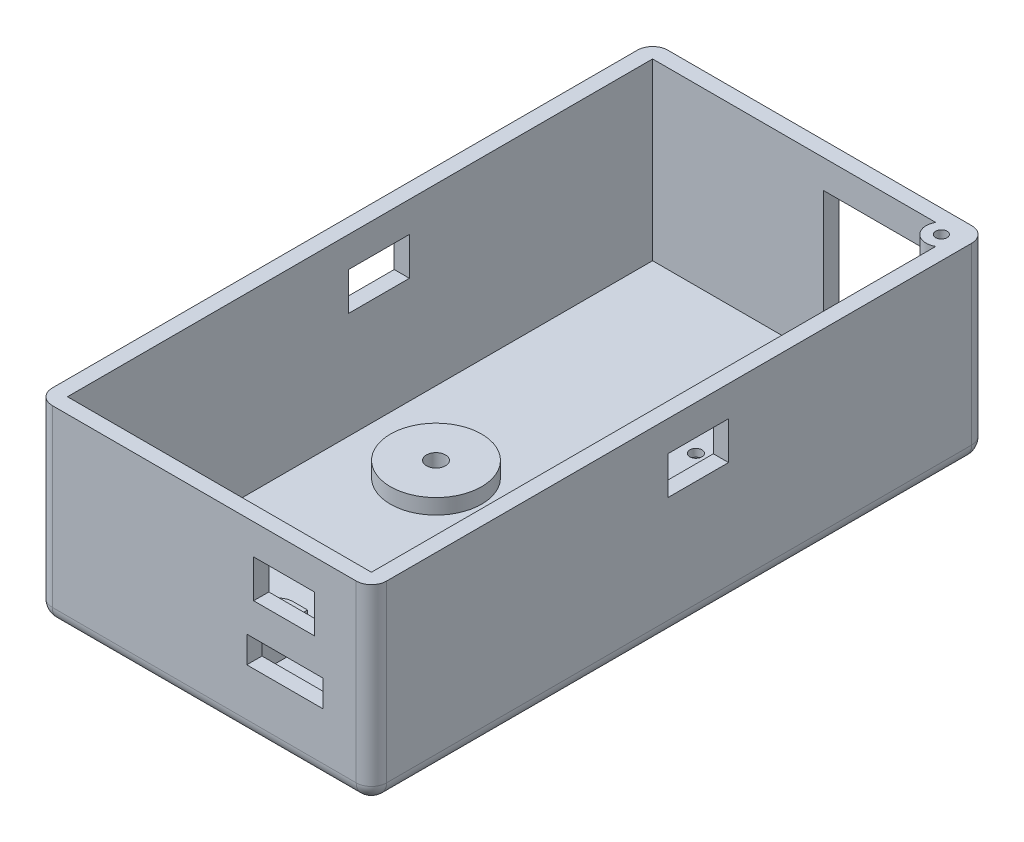
SolidWorks part; units mm, degrees
ref_plane "前视基准面" through (0, 0, 0) normal (0, 0, 1) x (1, 0, 0)
ref_plane "上视基准面" through (0, 0, 0) normal (0, 1, 0) x (1, 0, 0)
ref_plane "右视基准面" through (0, 0, 0) normal (1, 0, 0) x (0, 0, -1)
sketch "草图1" plane through (0, 0, 0) normal (0, 1, 0) x (1, 0, 0)
  line L1 (-22, 38) -> (22, 38)
  line L2 (-22, 38) -> (-22, -43)
  line L3 (-22, -43) -> (22, -43)
  line L4 (22, 38) -> (22, -43)
  dimension "D1" = 81
  dimension "D2" = 38
  dimension "D3" = 44
  dimension "D4" = 22
extrude "凸台-拉伸1" add sketch "草图1" along normal blind 25
shell "抽壳1" thickness 2 removed face at (0, 25, 2.5)
fillet "圆角1" radius 2 8 edges at (0, 0, -38) (0, 0, 43) (-22, 0, 2.5) (22, 0, 2.5) (-22, 12.5, 43) (-22, 12.5, -38) (22, 12.5, -38) (22, 12.5, 43)
sketch "草图2" plane through (0, 2, 0) normal (0, 1, 0) x (1, 0, 0)
  line L0 (20, 36) -> (-20, 36) construction
  line L1 (20, -41) -> (20, 36) construction
  line L2 (20, 36) -> (-20, 36) construction
  circle A0 centre (4.8, 16.9) radius 0.8
  circle A1 centre (16.1, -9.5) radius 0.9
  dimension "D1" = 19.1
  dimension "D3" = 45.5
  dimension "D2" = 15.2
  dimension "D4" = 3.9
extrude "切除-拉伸1" cut sketch "草图2" against normal blind 24
sketch "草图3" plane through (0, 2, 0) normal (0, 1, 0) x (1, 0, 0)
  line L1 (-20, 36) -> (-20, -41) construction
  line L2 (-20, -41) -> (20, -41) construction
  circle A0 centre (-9.5, -3) radius 1.25
  dimension "D3" = 2.5
  dimension "D1" = 10.5
  dimension "D2" = 38
extrude "切除-拉伸2" cut sketch "草图3" against normal blind 24
sketch "草图4" plane through (0, 2, 0) normal (0, 1, 0) x (1, 0, 0)
  circle A0 centre (-9.5, -3) radius 6
extrude "凸台-拉伸2" add sketch "草图4" along normal blind 2
sketch "草图6" plane through (0, 0, 0) normal (0, -1, 0) x (1, 0, 0)
  circle A0 centre (-9.5, 3) radius 1.25
extrude "切除-拉伸4" cut sketch "草图6" against normal blind 13.2
sketch "草图7" plane through (0, 0, -38) normal (0, 0, -1) x (-1, 0, 0)
  line L0 (20, 0) -> (-20, 0) construction
  line L1 (-18, 21.25) -> (-2.5, 21.25)
  line L2 (-18, 21.25) -> (-18, 3.75)
  line L3 (-18, 3.75) -> (-2.5, 3.75)
  line L4 (-2.5, 21.25) -> (-2.5, 3.75)
  line L5 (-22, 2) -> (-22, 25) construction
  dimension "D1" = 17.5
  dimension "D2" = 3.75
  dimension "D3" = 4
  dimension "D4" = 15.5
extrude "切除-拉伸5" cut sketch "草图7" against normal blind 13.2
sketch "草图9" plane through (0, 2, 0) normal (0, 1, 0) x (1, 0, 0)
  line L0 (-20, -41) -> (20, -41) construction
  line L1 (1.2, -34.5) -> (20, -34.5)
  line L2 (1.2, -34.5) -> (1.2, -41)
  line L3 (1.2, -41) -> (20, -41)
  line L4 (20, -34.5) -> (20, -41)
  line L5 (-20, -41) -> (20, -41) construction
  line L6 (22, -41) -> (22, 36) construction
  circle A0 centre (18.1, -37.9) radius 0.9
  circle A1 centre (3.1, -37.9) radius 0.9
  dimension "D7" = 1.8
  dimension "D8" = 1.8
  dimension "D1" = 15
  dimension "D2" = 1.9
  dimension "D3" = 3.1
  dimension "D4" = 6.5
  dimension "D5" = 1.9
  dimension "D6" = 2
  dimension "D9" = 3.1
  dimension "D10" = 18.8
extrude "凸台-拉伸3" add sketch "草图9" along normal blind 8 contours L2 L1 L4 L3 | A1 | A0
sketch "草图11" plane through (0, 10, 0) normal (0, 1, 0) x (1, 0, 0)
  line L0 (1.2, -34.5) -> (20, -34.5) construction
  line L1 (5.1, -34.5) -> (16.1, -34.5)
  line L2 (5.1, -34.5) -> (5.1, -41)
  line L3 (5.1, -41) -> (16.1, -41)
  line L4 (16.1, -34.5) -> (16.1, -41)
  line L5 (-20, -41) -> (20, -41) construction
  dimension "D1" = 11
  dimension "D2" = 3.9
extrude "切除-拉伸6" cut sketch "草图11" against normal blind 4
sketch "草图12" plane through (0, 0, 43) normal (0, 0, 1) x (1, 0, 0)
  line L0 (20, 0) -> (-20, 0) construction
  line L1 (5.6, 11.75) -> (15.6, 11.75)
  line L2 (5.6, 11.75) -> (5.6, 8.25)
  line L3 (5.6, 8.25) -> (15.6, 8.25)
  line L4 (15.6, 11.75) -> (15.6, 8.25)
  line L5 (22, 25) -> (22, 2) construction
  dimension "D1" = 10
  dimension "D2" = 3.5
  dimension "D3" = 8.25
  dimension "D4" = 6.4
extrude "切除-拉伸7" cut sketch "草图12" against normal blind 4
fillet "圆角2" radius 2 3 edges at (1.2, 2, 37.75) (10.6, 2, 34.5) (1.2, 6, 34.5)
sketch "草图14" plane through (0, 0, 0) normal (0, -1, 0) x (1, 0, 0)
  circle A0 centre (-9.5, 3) radius 1.25
extrude "凸台-拉伸4" add sketch "草图14" against normal blind 1
sketch "草图15" plane through (0, 0, 0) normal (0, -1, 0) x (1, 0, 0)
  circle A0 centre (16.1, 9.5) radius 2
  circle A1 centre (4.8, -16.9) radius 2
extrude "切除-拉伸8" cut sketch "草图15" against normal blind 1
sketch "草图16" plane through (-22, 0, 0) normal (-1, 0, 0) x (0, 0, 1)
  line L0 (-36, 25) -> (41, 25) construction
  line L1 (-4, 21) -> (4, 21)
  line L2 (-4, 21) -> (-4, 16)
  line L3 (-4, 16) -> (4, 16)
  line L4 (4, 21) -> (4, 16)
  dimension "D1" = 8
  dimension "D2" = 5
  dimension "D3" = 4
  dimension "D4" = 4
extrude "切除-拉伸9" cut sketch "草图16" against normal blind 59
sketch "草图17" plane through (0, 25, 0) normal (0, 1, 0) x (1, 0, 0)
  line L0 (20, 38) -> (-20, 38) construction
  line L1 (22, -41) -> (22, 36) construction
  circle A0 centre (19, 35) radius 2
  dimension "D1" = 4
  dimension "D2" = 3
  dimension "D3" = 3
extrude "凸台-拉伸5" add sketch "草图17" against normal blind 3
sketch "草图18" plane through (0, 25, 0) normal (0, 1, 0) x (1, 0, 0)
  circle A0 centre (19, 35) radius 0.75
extrude "切除-拉伸10" cut sketch "草图18" against normal blind 3
fillet "圆角3" radius 2 2 edges at (18.634, 22, -36) (20, 22, -34.634)
sketch "草图19" plane through (0, 0, 43) normal (0, 0, 1) x (1, 0, 0)
  line L0 (-20, 25) -> (20, 25) construction
  line L1 (6.5, 21) -> (14.5, 21)
  line L2 (6.5, 21) -> (6.5, 16)
  line L3 (6.5, 16) -> (14.5, 16)
  line L4 (14.5, 21) -> (14.5, 16)
  line L5 (22, 25) -> (22, 2) construction
  dimension "D1" = 8
  dimension "D2" = 5
  dimension "D3" = 4
  dimension "D4" = 7.5
extrude "切除-拉伸11" cut sketch "草图19" against normal blind 3
